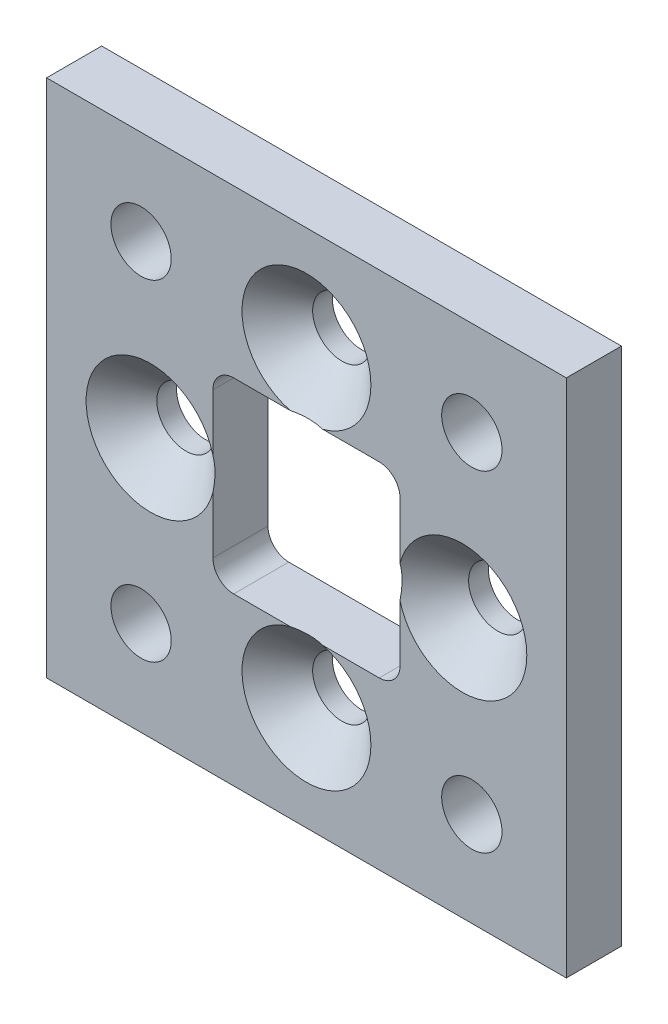
SolidWorks part; units mm, degrees
ref_plane "前视基准面" through (0, 0, 0) normal (0, 0, 1) x (1, 0, 0)
ref_plane "上视基准面" through (0, 0, 0) normal (0, 1, 0) x (1, 0, 0)
ref_plane "右视基准面" through (0, 0, 0) normal (1, 0, 0) x (0, 0, -1)
sketch "草图1" plane through (0, 0, 0) normal (0, 0, 1) x (1, 0, 0)
  line L1 (-12.5, 12.5) -> (12.5, 12.5)
  line L2 (-12.5, 12.5) -> (-12.5, -12.5)
  line L3 (-12.5, -12.5) -> (12.5, -12.5)
  line L4 (12.5, 12.5) -> (12.5, -12.5)
  line L5 (-12.5, 12.5) -> (12.5, -12.5) construction
  line L6 (-12.5, -12.5) -> (12.5, 12.5) construction
  line L7 (-4.5, 4.5) -> (4.5, 4.5)
  line L8 (-4.5, 4.5) -> (-4.5, -4.5)
  line L9 (-4.5, -4.5) -> (4.5, -4.5)
  line L10 (4.5, 4.5) -> (4.5, -4.5)
  line L11 (-4.5, 4.5) -> (4.5, -4.5) construction
  line L12 (-4.5, -4.5) -> (4.5, 4.5) construction
  circle A0 centre (0, 7.5) radius 1.4
  circle A1 centre (7.5, 0) radius 1.4
  circle A2 centre (0, -7.5) radius 1.4
  circle A3 centre (-7.5, 0) radius 1.4
  circle A4 centre (7.955, 7.955) radius 1.45
  circle A5 centre (7.955, -7.955) radius 1.45
  circle A6 centre (-7.955, -7.955) radius 1.45
  circle A7 centre (-7.955, 7.955) radius 1.45
  point P0 (0, 0)
  point P6 (0, 0)
  point P13 (-19.4332, 9.8082)
  point P14 (0, 0)
  point P22 (0, 0)
  point P31 (0, 0)
  dimension "D9" = 2.9
  dimension "D10" = 2.8
  dimension "D1" = 25
  dimension "D2" = 25
  dimension "D3" = 9
  dimension "D4" = 9
  dimension "D6" = 15
  dimension "D8" = 22.5
  dimension "D5" = 4
  dimension "D7" = 4
extrude "凸台-拉伸1" add sketch "草图1" along normal blind 2.65
chamfer "倒角1" distance 1.7 angle 45 4 edges at (1.4, 7.5, 2.65) (1.4, -7.5, 2.65) (8.9, 0, 2.65) (-6.1, 0, 2.65)
fillet "圆角1" radius 1 4 edges at (-4.5, -4.5, 1.325) (4.5, 4.5, 1.325) (4.5, -4.5, 1.325) (-4.5, 4.5, 1.325)
